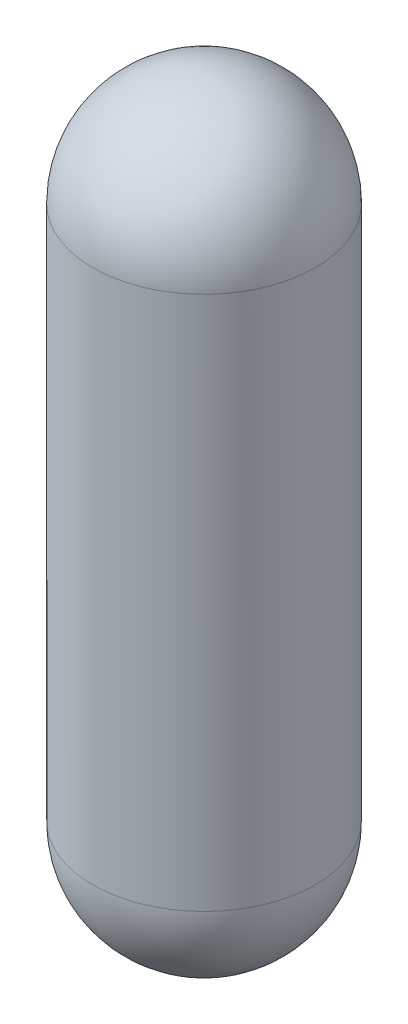
SolidWorks part; units mm, degrees
ref_plane "Front Plane" through (0, 0, 0) normal (0, 0, 1) x (1, 0, 0)
ref_plane "Top Plane" through (0, 0, 0) normal (0, 1, 0) x (1, 0, 0)
ref_plane "Right Plane" through (0, 0, 0) normal (1, 0, 0) x (0, 0, -1)
sketch "Sketch1" plane through (0, 0, 0) normal (0, 0, 1) x (1, 0, 0)
  line L0 (0, 1500) -> (0, 1812.5)
  line L2 (0, 0) -> (0, 1500)
  line L4 (312.5, 0) -> (312.5, 1500)
  line L5 (0, -312.5) -> (0, 0)
  arc A2 (312.5, 1500) -> (0, 1812.5) centre (0, 1500) ccw
  arc A3 (0, -312.5) -> (312.5, 0) centre (0, 0) ccw
  dimension "D3" = 1500
  dimension "D1" = 1500
  dimension "D2" = 312.5
  dimension "D5" = 312.5
  dimension "D6" = 312.5
revolve "Revolve1" add sketch "Sketch1" angle 360 about L2
